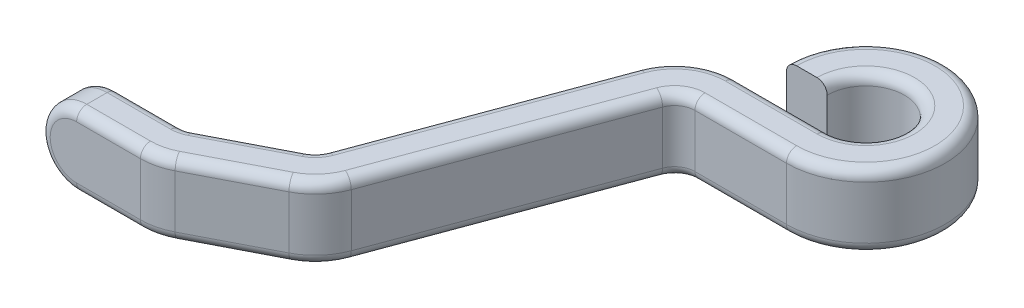
SolidWorks part; units mm, degrees
ref_plane "Front" through (0, 0, 0) normal (0, 0, 1) x (1, 0, 0)
ref_plane "Top" through (0, 0, 0) normal (0, 1, 0) x (1, 0, 0)
ref_plane "Right" through (0, 0, 0) normal (1, 0, 0) x (0, 0, -1)
sketch "Sketch1" plane through (0, 0, 0) normal (0, 0, 1) x (1, 0, 0)
  line L0 (5.3053, 0.9) -> (3.996, 0.9)
  line L1 (5.3053, -0.9) -> (5.3053, 0.9)
  line L2 (3.996, -0.9) -> (5.3053, -0.9)
  line L3 (5.4053, -1.0222) -> (5.4053, 1.0222)
  line L4 (5.3093, 0.95) -> (3.996, 0.95)
  line L5 (5.3093, 0.95) -> (3.996, 0.95) construction
  line L6 (5.4053, -1.0222) -> (5.4053, 1.0222) construction
  line L7 (3.996, -0.95) -> (5.3093, -0.95)
  line L8 (3.996, -0.95) -> (5.3093, -0.95) construction
  arc A0 (3.996, 0.9) -> (3.996, -0.9) centre (3.996, 0) ccw
  arc A1 (3.996, 0.95) -> (3.996, -0.95) centre (3.996, 0) ccw
  arc A2 (3.996, 0.95) -> (3.996, -0.95) centre (3.996, 0) ccw construction
  arc A21 (5.3093, 0.95) -> (5.4053, 1.0222) centre (5.3093, 1.05) ccw
  arc A22 (5.3093, 0.95) -> (5.4053, 1.0222) centre (5.3093, 1.05) ccw construction
  arc A23 (5.4053, -1.0222) -> (5.3093, -0.95) centre (5.3093, -1.05) ccw
  arc A24 (5.4053, -1.0222) -> (5.3093, -0.95) centre (5.3093, -1.05) ccw construction
  dimension "D1" = 0
  dimension "D2" = 0.1
extrude "Base-Extrude" add sketch "Sketch1" along normal blind 1
sketch "Sketch2" plane through (0, 0, 0) normal (0, 1, 0) x (1, 0, 0)
  line L0 (5.3053, -1) -> (5.3053, 0) construction
  line L1 (5.3053, -1) -> (5.3053, 0) construction
  line L2 (13.6003, 8.7927) -> (7.5184, 8.7927) construction
  line L3 (13.6003, 8.7927) -> (13.6003, 3.4625) construction
  line L4 (13.6003, 7.3427) -> (11.3503, 7.3427)
  line L5 (5.3053, -0.5) -> (5.5625, -0.5)
  line L6 (10.4125, 6.6898) -> (8.3456, 1.1052)
  line L7 (6.0211, -0.3886) -> (7.8664, 0.5637)
  arc A0 (7.8664, 0.5637) -> (8.3456, 1.1052) centre (7.4078, 1.4523) ccw
  circle A1 centre (13.6003, 8.7927) radius 0.95 construction
  circle A2 centre (13.6003, 8.7927) radius 0.95 construction
  arc A3 (13.6003, 7.3427) -> (12.1503, 8.7927) centre (13.6003, 8.7927) ccw
  arc A4 (6.0211, -0.3886) -> (5.5625, -0.5) centre (5.5625, 0.5) cw
  arc A5 (10.4125, 6.6898) -> (11.3503, 7.3427) centre (11.3503, 6.3427) cw
sketch "Sketch3" plane through (5.3053, 0, 0) normal (1, 0, 0) x (0, 0, -1)
  line L4 (0, -0.9) -> (0, 0.9)
  line L5 (0, 0.9) -> (-1, 0.9)
  line L6 (-1, 0.9) -> (-1, -0.9)
  line L7 (-1, -0.9) -> (0, -0.9)
  line L8 (0, -0.9) -> (0, 0.9)
  line L9 (0, 0.9) -> (-1, 0.9)
  line L10 (-1, 0.9) -> (-1, -0.9)
  line L11 (-1, -0.9) -> (0, -0.9)
  dimension "D1" = 0
sweep "Boss-Sweep1" add profiles "Sketch3" path "Sketch2"
fillet "Fillet2" radius 0.25 17 edges at (14.9792, -0.9, -10.1715) (12.4753, -0.9, -6.8427) (11.0646, -0.9, -6.753) (9.848, -0.9, -3.7239) (4.7793, -0.9, 1) (3.096, 0, 1) (14.9792, 0.9, -10.1715) (4.7793, 0.9, 1) (12.4753, 0.9, -6.8427) (11.0646, 0.9, -6.753) (9.848, 0.9, -3.7239) (8.5311, -0.9, -0.4582) (7.173, -0.9, 0.3568) (5.9164, -0.9, 0.9576) (5.9164, 0.9, 0.9576) (7.173, 0.9, 0.3568) (8.5311, 0.9, -0.4582)
fillet "Fillet3" radius 0.25 17 edges at (14.2721, -0.9, -9.4644) (12.4753, -0.9, -7.8427) (10.4933, -0.9, -7.5737) (8.9101, -0.9, -4.071) (4.7793, -0.9, 0) (3.096, 0, 0) (14.2721, 0.9, -9.4644) (4.7793, 0.9, 0) (12.4753, 0.9, -7.8427) (10.4933, 0.9, -7.5737) (8.9101, 0.9, -4.071) (7.7822, -0.9, -1.121) (6.7144, -0.9, -0.5318) (5.6805, -0.9, -0.0141) (5.6805, 0.9, -0.0141) (6.7144, 0.9, -0.5318) (7.7822, 0.9, -1.121)
